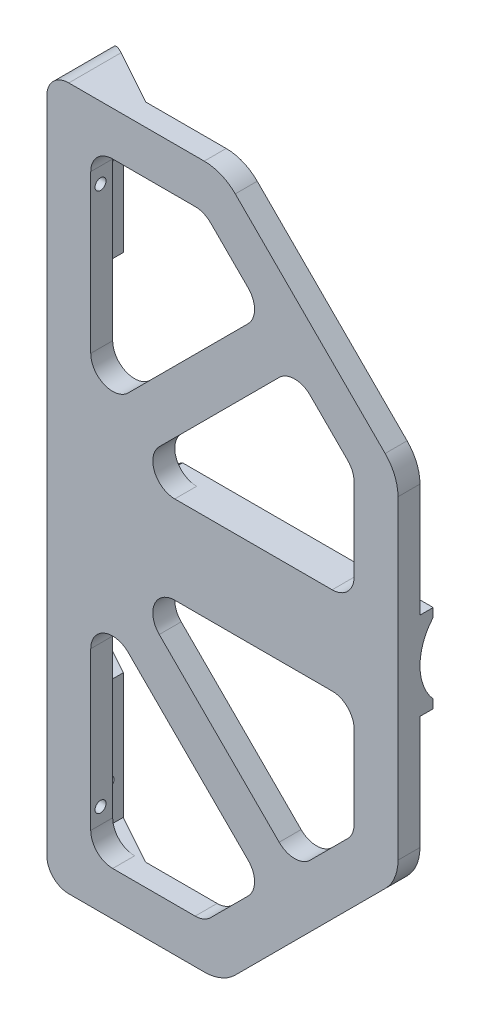
SolidWorks part; units mm, degrees
ref_plane "Plano frontal" through (0, 0, 0) normal (0, 0, 1) x (1, 0, 0)
ref_plane "Plano superior" through (0, 0, 0) normal (0, 1, 0) x (1, 0, 0)
ref_plane "Plano direito" through (0, 0, 0) normal (1, 0, 0) x (0, 0, -1)
sketch "Esboço1" plane through (0, 0, 0) normal (0, 0, 1) x (1, 0, 0)
  line L4 (-148.8701, 85.1486) -> (-188.8701, 125.1486)
  line L5 (-188.8701, 125.1486) -> (-228.8701, 125.1486)
  line L6 (-148.8701, 85.1486) -> (-148.8701, 5.1664)
  line L9 (-188.8701, -34.8336) -> (-228.8701, -34.8336)
  line L10 (-228.8701, 125.1486) -> (-228.8701, -34.8336)
  line L11 (-148.8701, 5.1664) -> (-188.8701, -34.8336)
  point P7 (-148.8701, 125.1486)
  point P10 (-148.8701, -34.8336)
  dimension "D1" = 80
extrude "Ressalto-extrusão2" add sketch "Esboço1" along normal blind 5
sketch "Esboço4" plane through (0, 0, 0) normal (0, 0, -1) x (-1, 0, 0)
  line L0 (188.8701, 125.1486) -> (148.8701, 85.1486)
  line L1 (148.8701, 85.1486) -> (148.8701, 5.1664)
  line L2 (148.8701, 5.1664) -> (188.8701, -34.8336)
  line L3 (188.8701, -34.8336) -> (228.8701, -34.8336)
  line L4 (228.8701, -34.8336) -> (228.8701, 125.1486)
  line L5 (228.8701, 125.1486) -> (188.8701, 125.1486)
  line L6 (193.0122, 115.1486) -> (158.8701, 81.0065)
  line L7 (158.8701, 81.0065) -> (158.8701, 9.3086)
  line L8 (158.8701, 9.3086) -> (193.0122, -24.8336)
  line L9 (193.0122, -24.8336) -> (218.8701, -24.8336)
  line L10 (218.8701, -24.8336) -> (218.8701, 115.1486)
  line L11 (218.8701, 115.1486) -> (193.0122, 115.1486)
  line L12 (158.8701, 45.1575) -> (218.8701, 45.1575) construction
  line L13 (218.8701, 55.1486) -> (158.8701, 55.1486)
  line L14 (218.8701, 35.1664) -> (158.8701, 35.1664)
  line L15 (175.9412, 98.0775) -> (218.8701, 55.1486) construction
  line L16 (175.5405, 105.5493) -> (231.6611, 49.4286)
  line L17 (168.4694, 98.4782) -> (224.5901, 42.3576)
  line L18 (168.4694, -8.1632) -> (224.5901, 47.9575)
  line L19 (175.5405, -15.2342) -> (231.6611, 40.8864)
  dimension "D1" = 10
  dimension "D2" = 5
extrude "Corte-extrusão1" cut sketch "Esboço4" against normal blind 5 contours L6 L16 L10 L11 | L17 L6 L7 L13 | L8 L18 L14 L7 | L19 L8 L9 L10 region at (-204.5001, 95.5297, 0) region at (-204.5001, -5.2146, 0) region at (-178.489, 69.5186, 0) region at (-178.489, 20.7964, 0)
fillet "Filete1" radius 10 4 edges at (-188.8701, 125.1486, 2.5) (-148.8701, 85.1486, 2.5) (-188.8701, -34.8336, 2.5) (-148.8701, 5.1664, 2.5)
fillet "Filete2" radius 5 2 edges at (-218.8701, -24.8336, 2.5) (-218.8701, 115.1486, 2.5)
sketch "Esboço7" plane through (0, 0, 0) normal (0, 0, -1) x (-1, 0, 0)
  line L1 (148.8701, 55.1486) -> (211.799, 55.1486)
  line L2 (148.8701, 55.1486) -> (148.8701, 35.1664)
  line L3 (148.8701, 35.1664) -> (211.799, 35.1664)
  line L4 (211.799, 55.1486) -> (211.799, 35.1664)
  line L7 (211.799, 55.1486) -> (158.8701, 55.1486) construction
  line L8 (148.8701, 9.3086) -> (148.8701, 81.0065) construction
extrude "Ressalto-extrusão5" add sketch "Esboço7" along normal blind 5
sketch "Esboço8" plane through (-148.8701, 0, 0) normal (1, 0, 0) x (0, 0, -1)
  line L0 (0, 55.1486) -> (0, 35.1664) construction
  line L1 (0, 45.1575) -> (29.1685, 45.1575) construction
  line L2 (3.0093, 58.6903) -> (3.0093, 25.6838)
  circle A0 centre (12.3, 45.1575) radius 12.3
  line M2 (0, 35.1664) -> (5, 35.1664)
  line M3 (5, 35.1664) -> (5, 55.1486)
  line M4 (5, 55.1486) -> (0, 55.1486)
  dimension "D1" = 24.6
extrude "Corte-extrusão2" cut sketch "Esboço8" against normal blind 66 contours L2 A0 | A0 L2 M3 M4 | A0 L2 M3 | A0 L2 M2 M3 region at (-148.8701, 54.5285, -3.6826) region at (-148.8701, 45.1575, -4.0382) region at (-148.8701, 45.1575, -1.792) region at (-148.8701, 35.7865, -3.6826)
fillet "Filete3" radius 5 14 edges at (-218.8701, 62.2197, 2.5) (-211.799, 55.1486, 2.5) (-211.799, 35.1664, 2.5) (-218.8701, 28.0954, 2.5) (-193.0122, -24.8336, 2.5) (-179.4767, -11.298, 2.5) (-172.4056, -4.227, 2.5) (-158.8701, 9.3086, 2.5) (-179.4767, 101.6131, 2.5) (-193.0122, 115.1486, 2.5) (-158.8701, 81.0065, 2.5) (-172.4056, 94.542, 2.5)
sketch "Esboço9" plane through (0, 0, 0) normal (0, 0, -1) x (-1, 0, 0)
  line L0 (199.7562, 56.8754) -> (138.366, 63.924)
  line L1 (138.366, 63.924) -> (138.366, 23.2619)
  line L2 (138.366, 23.2619) -> (199.7562, 32.8448)
  circle A0 centre (199.7562, 44.8601) radius 12.0153
  line M1 (211.799, 55.1486) -> (211.799, 45.1575)
  line M2 (211.799, 45.1575) -> (211.799, 35.1664)
  line M3 (211.799, 35.1664) -> (199.728, 35.1664)
  arc M4 (199.728, 35.1664) -> (203.2635, 26.6309) centre (199.728, 30.1664) cw
  line M5 (203.2635, 26.6309) -> (175.9412, -0.6914)
  arc M6 (175.9412, -0.6914) -> (168.8701, -0.6914) centre (172.4056, 2.8441) cw
  line M7 (168.8701, -0.6914) -> (160.3346, 7.8441)
  arc M8 (160.3346, 7.8441) -> (158.8701, 11.3796) centre (163.8701, 11.3796) cw
  line M9 (158.8701, 11.3796) -> (158.8701, 30.1664)
  line M12 (148.8701, 35.1664) -> (148.8701, 9.3086)
  arc M13 (148.8701, 9.3086) -> (151.799, 2.2375) centre (158.8701, 9.3086) ccw
  line M14 (151.799, 2.2375) -> (185.9412, -31.9046)
  arc M15 (185.9412, -31.9046) -> (193.0122, -34.8336) centre (193.0122, -24.8336) ccw
  line M16 (193.0122, -34.8336) -> (228.8701, -34.8336)
  line M18 (228.8701, -34.8336) -> (228.8701, 125.1486)
  line M20 (228.8701, 125.1486) -> (193.0122, 125.1486)
  arc M21 (193.0122, 125.1486) -> (185.9412, 122.2197) centre (193.0122, 115.1486) ccw
  line M22 (185.9412, 122.2197) -> (151.799, 88.0775)
  arc M23 (151.799, 88.0775) -> (148.8701, 81.0065) centre (158.8701, 81.0065) ccw
  line M24 (148.8701, 81.0065) -> (148.8701, 55.1486)
  line M27 (158.8701, 60.1486) -> (158.8701, 78.9354)
  arc M28 (158.8701, 78.9354) -> (160.3346, 82.4709) centre (163.8701, 78.9354) cw
  line M29 (160.3346, 82.4709) -> (168.8701, 91.0065)
  arc M30 (168.8701, 91.0065) -> (175.9412, 91.0065) centre (172.4056, 87.4709) cw
  line M31 (175.9412, 91.0065) -> (203.2635, 63.6841)
  arc M32 (203.2635, 63.6841) -> (199.728, 55.1486) centre (199.728, 60.1486) cw
  line M33 (199.728, 55.1486) -> (211.799, 55.1486)
  line M34 (191.5478, -23.3691) -> (183.0122, -14.8336)
  arc M35 (183.0122, -14.8336) -> (183.0122, -7.7625) centre (186.5478, -11.298) cw
  line M36 (183.0122, -7.7625) -> (210.3346, 19.5598)
  arc M37 (210.3346, 19.5598) -> (218.8701, 16.0243) centre (213.8701, 16.0243) cw
  line M38 (218.8701, 16.0243) -> (218.8701, -19.8336)
  arc M39 (218.8701, -19.8336) -> (213.8701, -24.8336) centre (213.8701, -19.8336) cw
  line M40 (213.8701, -24.8336) -> (195.0833, -24.8336)
  arc M41 (195.0833, -24.8336) -> (191.5478, -23.3691) centre (195.0833, -19.8336) cw
  line M42 (210.3346, 70.7552) -> (183.0122, 98.0775)
  arc M43 (183.0122, 98.0775) -> (183.0122, 105.1486) centre (186.5478, 101.6131) cw
  line M44 (183.0122, 105.1486) -> (191.5478, 113.6841)
  arc M45 (191.5478, 113.6841) -> (195.0833, 115.1486) centre (195.0833, 110.1486) cw
  line M46 (195.0833, 115.1486) -> (213.8701, 115.1486)
  arc M47 (213.8701, 115.1486) -> (218.8701, 110.1486) centre (213.8701, 110.1486) cw
  line M48 (218.8701, 110.1486) -> (218.8701, 74.2907)
  arc M49 (218.8701, 74.2907) -> (210.3346, 70.7552) centre (213.8701, 74.2907) cw
extrude "Corte-extrusão5" cut sketch "Esboço9" along normal blind 35 contours A0 L2 L0 M33 M1 M2 M3 M4 M5 M6 M7 M8 M9 M12 M13 M14 M15 M16 M18 M20 M21 M22 M23 M24 M27 M28 M29 M30 M31 M32 M41 M34 M35 M36 M37 M38 M39 M40 M49 M42 M43 M44 M45 M46 M47 M48 | A0 M3 M2 M1 M33 region at (-154.0741, 63.9209, 0) region at (-208.8806, 54.9404, 0)
sketch "Esboço10" plane through (0, -34.8336, 0) normal (0, -1, 0) x (1, 0, 0)
  line L0 (-211.3584, 0) -> (-228.8701, 0)
  line L1 (-228.8701, 0) -> (-193.0122, 0) construction
  line L2 (-228.8701, 0) -> (-228.8701, -9.6677)
  line L3 (-228.8701, -9.6677) -> (-211.3584, 0)
  line L4 (-228.8701, 5) -> (-228.8701, 0) construction
  line L5 (-228.8701, 0) -> (-193.0122, 0) construction
extrude "Ressalto-extrusão6" add sketch "Esboço10" against normal through all
sketch "Esboço12" plane through (0, 0, 0) normal (0, 0, 1) x (1, 0, 0)
  line L1 (-211.3584, 115.1486) -> (-222.7417, 115.1486)
  line L2 (-211.3584, 115.1486) -> (-211.3584, -24.8336)
  line L3 (-211.3584, -24.8336) -> (-222.7417, -24.8336)
  line L4 (-222.7417, 115.1486) -> (-222.7417, -24.8336)
extrude "Corte-extrusão6" cut sketch "Esboço12" against normal blind 10
sketch "Esboço14" plane through (-222.7417, 0, 0) normal (1, 0, 0) x (0, 0, -1)
  line L0 (-2.7684, 106.5685) -> (6.2844, 106.5685) construction
  line L1 (6.2844, -24.8336) -> (6.2844, 115.1486) construction
  line L2 (6.2844, 45.1575) -> (0, 45.1575) construction
  line L3 (0, 115.1486) -> (0, -24.8336) construction
  circle A0 centre (2.9346, 106.5685) radius 1.25
  circle A1 centre (-2.7684, 106.5685) radius 1.25
  circle A2 centre (-2.7684, -16.2534) radius 1.25
  circle A3 centre (2.9346, -16.2534) radius 1.25
  dimension "D1" = 2.5
  dimension "D2" = 2.5
extrude "Corte-extrusão7" cut sketch "Esboço14" against normal through all and the other way blind 10
fillet "Filete4" radius 5 2 edges at (-228.8701, -34.8336, -2.3338) (-228.8701, 125.1486, -2.3338)
sketch "Esboço16" plane through (0, 0, 0) normal (0, 0, -1) x (-1, 0, 0)
  line L0 (222.7417, 115.1486) -> (222.7417, -24.8336) construction
  line L1 (207.7196, 86.6063) -> (237.7639, 86.6063)
  line L2 (207.7196, 86.6063) -> (207.7196, 3.7087)
  line L3 (207.7196, 3.7087) -> (237.7639, 3.7087)
  line L4 (237.7639, 86.6063) -> (237.7639, 3.7087)
  line L5 (207.7196, 86.6063) -> (237.7639, 3.7087) construction
  line L6 (207.7196, 3.7087) -> (237.7639, 86.6063) construction
  point P0 (222.7417, 45.1575)
extrude "Corte-extrusão8" cut sketch "Esboço16" along normal through all
